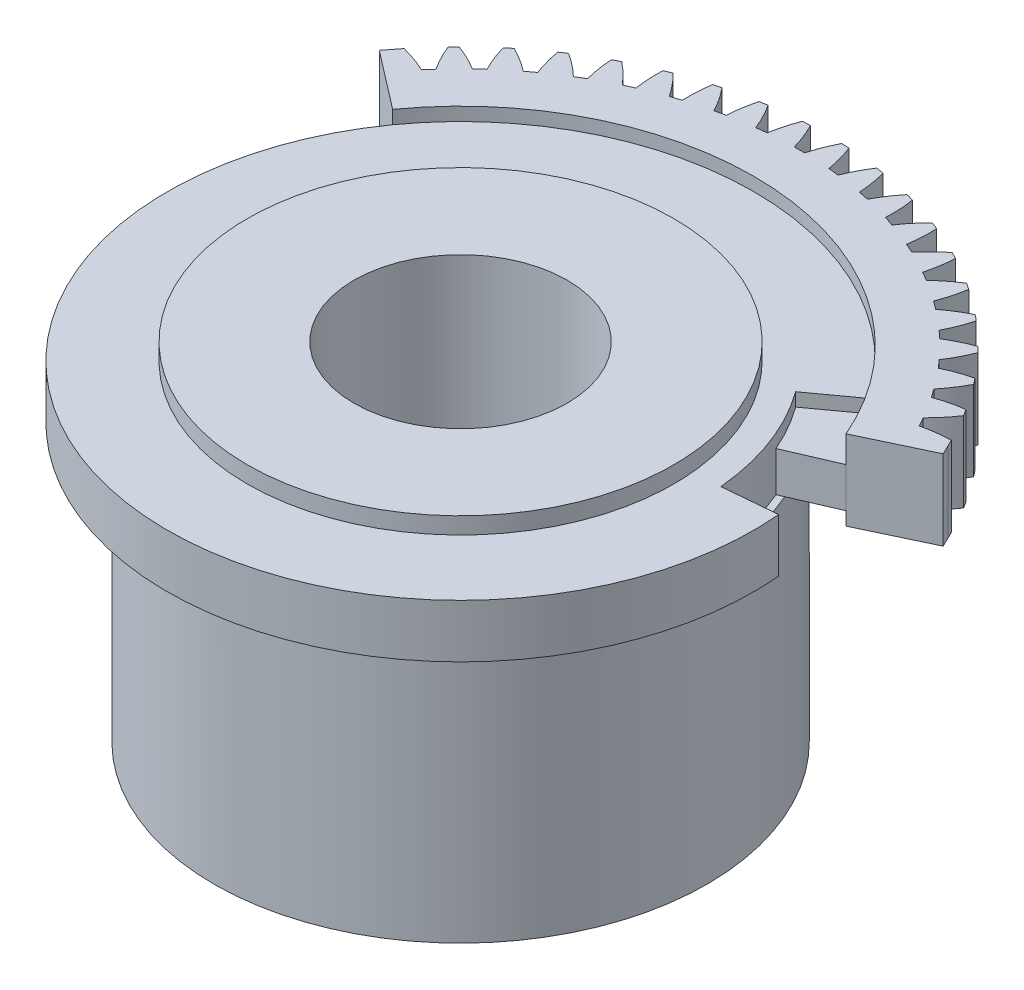
SolidWorks part; units mm, degrees
ref_plane "Front Plane" through (0, 0, 0) normal (0, 0, 1) x (1, 0, 0)
ref_plane "Top Plane" through (0, 0, 0) normal (0, 1, 0) x (1, 0, 0)
ref_plane "Right Plane" through (0, 0, 0) normal (1, 0, 0) x (0, 0, -1)
sketch "Sketch1" plane through (0, 0, 0) normal (0, 1, 0) x (1, 0, 0)
  line L0 (16.523, 7.1407) -> (20.1948, 8.7275)
  line L1 (17.8057, 12.9211) -> (14.5683, 10.5718)
  line L2 (15.3777, 11.1592) -> (17.8057, 12.9211)
  line L3 (21.913, 1.955) -> (17.9288, 1.5995)
  line L4 (-22.2321, 16.1317) -> (-17.8936, 12.7991)
  line L5 (20.1948, 8.7275) -> (25.1397, 11.0677)
  line L6 (25.1397, 11.0677) -> (24.8118, 11.7422)
  line L7 (-21.769, 16.7216) -> (-22.2321, 16.1317)
  arc A1 (20.1948, 8.7275) -> (17.8057, 12.9211) centre (0, 0) ccw
  circle A2 centre (0, 0) radius 8
  circle A3 centre (0, 0) radius 16
  arc A5 (17.8057, 12.9211) -> (-17.8936, 12.7991) centre (0, 0) ccw
  arc A6 (-17.8936, 12.7991) -> (21.913, 1.955) centre (0, 0) ccw
  arc A7 (20.1948, 8.7275) -> (-17.8936, 12.7991) centre (0, 0) ccw
  arc A8 (24.8118, 11.7422) -> (24.5577, 12.2646) centre (0, 0) ccw
  arc A9 (24.5577, 12.2646) -> (22.4251, 11.979) centre (24.8942, 1.65) ccw
  arc A10 (22.4251, 11.979) -> (22.0497, 12.6566) centre (0, 0) ccw
  arc A11 (22.0497, 12.6566) -> (23.4231, 14.313) centre (14.6032, 20.2285) ccw
  arc A12 (23.4231, 14.313) -> (23.1149, 14.8055) centre (0, 0) ccw
  arc A13 (23.1149, 14.8055) -> (21.0248, 14.2947) centre (24.5778, 4.2867) ccw
  arc A14 (21.0248, 14.2947) -> (20.5795, 14.9287) centre (0, 0) ccw
  arc A15 (20.5795, 14.9287) -> (21.769, 16.7216) centre (12.3703, 21.6661) ccw
  arc A16 (21.769, 16.7216) -> (21.4103, 17.1786) centre (0, 0) ccw
  arc A17 (21.4103, 17.1786) -> (19.3862, 16.4485) centre (23.9829, 6.8749) ccw
  arc A18 (19.3862, 16.4485) -> (18.8761, 17.0316) centre (0, 0) ccw
  arc A19 (18.8761, 17.0316) -> (19.8683, 18.9408) centre (9.9972, 22.8583) ccw
  arc A20 (19.8683, 18.9408) -> (19.463, 19.357) centre (0, 0) ccw
  arc A21 (19.463, 19.357) -> (17.528, 18.416) centre (23.1163, 9.3852) ccw
  arc A22 (17.528, 18.416) -> (16.9588, 18.9415) centre (0, 0) ccw
  arc A23 (16.9588, 18.9415) -> (17.7424, 20.9454) centre (7.5109, 23.7914) ccw
  arc A24 (17.7424, 20.9454) -> (17.2952, 21.3162) centre (0, 0) ccw
  arc A25 (17.2952, 21.3162) -> (15.4712, 20.1748) centre (21.9878, 11.7891) ccw
  arc A26 (15.4712, 20.1748) -> (14.8494, 20.6368) centre (0, 0) ccw
  arc A27 (14.8494, 20.6368) -> (15.4156, 22.7126) centre (4.9395, 24.455) ccw
  arc A28 (15.4156, 22.7126) -> (14.9315, 23.0338) centre (0, 0) ccw
  arc A29 (14.9315, 23.0338) -> (13.2391, 21.705) centre (20.6101, 14.0595) ccw
  arc A30 (13.2391, 21.705) -> (12.5717, 22.0983) centre (0, 0) ccw
  arc A31 (12.5717, 22.0983) -> (12.914, 24.2225) centre (2.3121, 24.8415) ccw
  arc A32 (12.914, 24.2225) -> (12.3985, 24.4904) centre (0, 0) ccw
  arc A33 (12.3985, 24.4904) -> (10.857, 22.9892) centre (18.9989, 16.1706) ccw
  arc A34 (10.857, 22.9892) -> (10.1516, 23.3093) centre (0, 0) ccw
  arc A35 (10.1516, 23.3093) -> (10.2662, 25.458) centre (-0.3415, 24.9465) ccw
  arc A36 (10.2662, 25.458) -> (9.7251, 25.6695) centre (0, 0) ccw
  arc A37 (9.7251, 25.6695) -> (8.3519, 24.013) centre (17.1724, 18.0984) ccw
  arc A38 (8.3519, 24.013) -> (7.6164, 24.2563) centre (0, 0) ccw
  arc A39 (7.6164, 24.2563) -> (7.502, 26.405) centre (-2.9912, 24.7689) ccw
  arc A40 (7.502, 26.405) -> (6.9415, 26.5578) centre (0, 0) ccw
  arc A41 (6.9415, 26.5578) -> (5.7522, 24.7647) centre (15.1514, 19.8212) ccw
  arc A42 (5.7522, 24.7647) -> (4.995, 24.9285) centre (0, 0) ccw
  arc A43 (4.995, 24.9285) -> (4.6528, 27.0528) centre (-5.607, 24.3106) ccw
  arc A44 (4.6528, 27.0528) -> (4.0793, 27.1452) centre (0, 0) ccw
  arc A45 (4.0793, 27.1452) -> (3.0872, 25.2359) centre (12.9587, 21.3194) ccw
  arc A46 (3.0872, 25.2359) -> (2.3169, 25.3182) centre (0, 0) ccw
  arc A47 (2.3169, 25.3182) -> (1.7509, 27.3941) centre (-8.1593, 23.5769) ccw
  arc A48 (1.7509, 27.3941) -> (1.1708, 27.425) centre (0, 0) ccw
  arc A49 (1.1708, 27.425) -> (0.3874, 25.421) centre (10.6192, 22.576) ccw
  arc A50 (0.3874, 25.421) -> (-0.3874, 25.421) centre (0, 0) ccw
  arc A51 (-0.3874, 25.421) -> (-1.1708, 27.425) centre (-10.6192, 22.576) ccw
  arc A52 (-1.1708, 27.425) -> (-1.7509, 27.3941) centre (0, 0) ccw
  arc A53 (-1.7509, 27.3941) -> (-2.3169, 25.3182) centre (8.1593, 23.5769) ccw
  arc A54 (-2.3169, 25.3182) -> (-3.0872, 25.2359) centre (0, 0) ccw
  arc A55 (-3.0872, 25.2359) -> (-4.0793, 27.1452) centre (-12.9587, 21.3194) ccw
  arc A56 (-4.0793, 27.1452) -> (-4.6528, 27.0528) centre (0, 0) ccw
  arc A57 (-4.6528, 27.0528) -> (-4.995, 24.9285) centre (5.607, 24.3106) ccw
  arc A58 (-4.995, 24.9285) -> (-5.7522, 24.7647) centre (0, 0) ccw
  arc A59 (-5.7522, 24.7647) -> (-6.9415, 26.5578) centre (-15.1514, 19.8212) ccw
  arc A60 (-6.9415, 26.5578) -> (-7.502, 26.405) centre (0, 0) ccw
  arc A61 (-7.502, 26.405) -> (-7.6164, 24.2563) centre (2.9912, 24.7689) ccw
  arc A62 (-7.6164, 24.2563) -> (-8.3519, 24.013) centre (0, 0) ccw
  arc A63 (-8.3519, 24.013) -> (-9.7251, 25.6695) centre (-17.1724, 18.0984) ccw
  arc A64 (-9.7251, 25.6695) -> (-10.2662, 25.458) centre (0, 0) ccw
  arc A65 (-10.2662, 25.458) -> (-10.1516, 23.3093) centre (0.3415, 24.9465) ccw
  arc A66 (-10.1516, 23.3093) -> (-10.857, 22.9892) centre (0, 0) ccw
  arc A67 (-10.857, 22.9892) -> (-12.3985, 24.4904) centre (-18.9989, 16.1706) ccw
  arc A68 (-12.3985, 24.4904) -> (-12.914, 24.2225) centre (0, 0) ccw
  arc A69 (-12.914, 24.2225) -> (-12.5717, 22.0983) centre (-2.3121, 24.8415) ccw
  arc A70 (-12.5717, 22.0983) -> (-13.2391, 21.705) centre (0, 0) ccw
  arc A71 (-13.2391, 21.705) -> (-14.9315, 23.0338) centre (-20.6101, 14.0595) ccw
  arc A72 (-14.9315, 23.0338) -> (-15.4156, 22.7126) centre (0, 0) ccw
  arc A73 (-15.4156, 22.7126) -> (-14.8494, 20.6368) centre (-4.9395, 24.455) ccw
  arc A74 (-14.8494, 20.6368) -> (-15.4712, 20.1748) centre (0, 0) ccw
  arc A75 (-15.4712, 20.1748) -> (-17.2952, 21.3162) centre (-21.9878, 11.7891) ccw
  arc A76 (-17.2952, 21.3162) -> (-17.7424, 20.9454) centre (0, 0) ccw
  arc A77 (-17.7424, 20.9454) -> (-16.9588, 18.9415) centre (-7.5109, 23.7914) ccw
  arc A78 (-16.9588, 18.9415) -> (-17.528, 18.416) centre (0, 0) ccw
  arc A79 (-17.528, 18.416) -> (-19.463, 19.357) centre (-23.1163, 9.3852) ccw
  arc A80 (-19.463, 19.357) -> (-19.8683, 18.9408) centre (0, 0) ccw
  arc A81 (-19.8683, 18.9408) -> (-18.8761, 17.0316) centre (-9.9972, 22.8583) ccw
  arc A82 (-18.8761, 17.0316) -> (-19.3862, 16.4485) centre (0, 0) ccw
  arc A83 (-19.3862, 16.4485) -> (-21.4103, 17.1786) centre (-23.9829, 6.8749) ccw
  arc A84 (-21.4103, 17.1786) -> (-21.769, 16.7216) centre (0, 0) ccw
  arc A85 (17.9288, 1.5995) -> (14.5683, 10.5718) centre (0, 0) ccw
extrude "Boss-Extrude1" add sketch "Sketch1" along normal blind 6 contours A83 A84 L7 L4 A5 A1 L5 L6 A8 A9 A10 A11 A12 A13 A14 A15 A16 A17 A18 A19 A20 A21 A22 A23 A24 A25 A26 A27 A28 A29 A30 A31 A32 A33 A34 A35 A36 A37 A38 A39 A40 A41 A42 A43 A44 A45 A46 A47 A48 A49 A50 region at (19.5581, 0, -11.1421)
extrude "Boss-Extrude2" add sketch "Sketch1<3>" along normal blind 4 from offset 1 contours A5 A6 L3 L1 A3 | L0 A1 L1 region at (17.4007, 0, -9.913) region at (16.8441, 0, -4.2733)
sketch "Sketch1<3>" plane through (0, 0, 0) normal (0, 1, 0) x (1, 0, 0) same geometry as "Sketch1"
extrude "Cut-Extrude2" cut sketch "Sketch1<4>" against normal blind 1 from surface starting at face at (0, 5, 16)
sketch "Sketch1<4>" plane through (0, 0, 0) normal (0, 1, 0) x (1, 0, 0) same geometry as "Sketch1"
extrude "Boss-Extrude3" add sketch "Sketch1<5>" along normal offset from surface (6.25 mm away) 0.25 contours A3 A2 region at (-15.5475, 0, 0) up to face at (2.2983, 6, -21.4994) offset beyond the face yes
sketch "Sketch1<5>" plane through (0, 0, 0) normal (0, 1, 0) x (1, 0, 0) same geometry as "Sketch1"
sketch "Sketch2" plane through (0, 1, 0) normal (0, -1, 0) x (1, 0, 0)
  circle A0 centre (0, 0) radius 18.5
  dimension "D1" = 37
extrude "Boss-Extrude4" add sketch "Sketch2" along normal blind 20.75
extrude "Cut-Extrude3" cut sketch "Sketch1<6>" against normal blind 13 from surface contours A2 region at (0, 0, 0) starting at face at (0, 6.25, 8)
sketch "Sketch1<6>" plane through (0, 0, 0) normal (0, 1, 0) x (1, 0, 0) same geometry as "Sketch1"
sketch "Sketch3" plane through (0, -19.75, 0) normal (0, -1, 0) x (1, 0, 0)
  circle A0 centre (0, 0) radius 5
  dimension "D1" = 10
extrude "Cut-Extrude4" cut sketch "Sketch3" against normal offset from surface (11 mm away) 2 up to face at (0, -6.75, 8)
sketch "Sketch4" plane through (0, -19.75, 0) normal (0, -1, 0) x (1, 0, 0)
  point P0 (0, 0)
